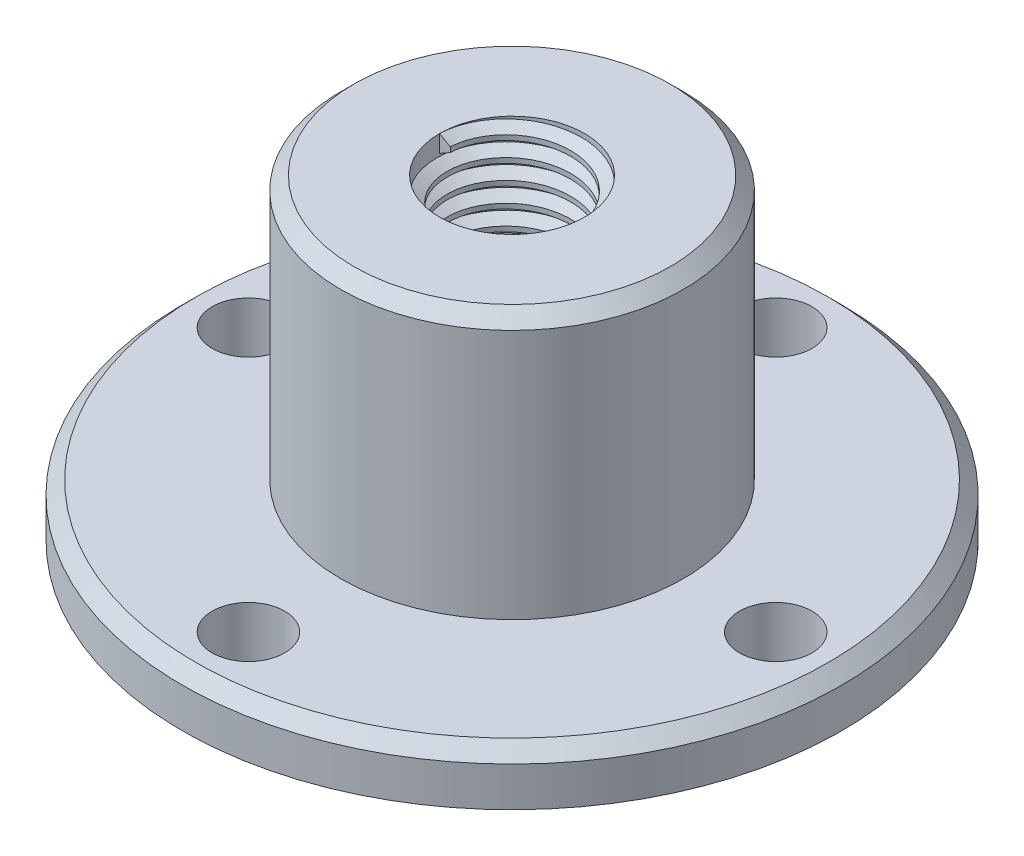
SolidWorks part; units mm, degrees
material "6061 Legierung"
ref_plane "Ebene vorne" through (0, 0, 0) normal (0, 0, 1) x (1, 0, 0)
ref_plane "Ebene oben" through (0, 0, 0) normal (0, 1, 0) x (1, 0, 0)
ref_plane "Ebene rechts" through (0, 0, 0) normal (1, 0, 0) x (0, 0, -1)
sketch "Skizze1" plane through (0, 0, 0) normal (0, 1, 0) x (1, 0, 0)
  circle A0 centre (0, 0) radius 13
  circle A1 centre (0, 0) radius 5.5
  dimension "D1" = 26
  dimension "D2" = 11
extrude "Aufsatz-Linear austragen1" add sketch "Skizze1" along normal blind 20
sketch "Skizze5" plane through (0, 0, 0) normal (0, -1, 0) x (1, 0, 0)
  circle A0 centre (0, 0) radius 25
  circle A2 centre (0, 0) radius 5.5
  dimension "D1" = 50
extrude "Aufsatz-Linear austragen2" add sketch "Skizze5" along normal blind 4
thread "Gewinde1" pitch 1.5 method extrude profile "Gewindeprofil1" start angle 0, offset 0, length 0, pitch 1.5, diameter 11
ref_plane "Ebene1" through (-5.5, 20, 0) normal (0, 0, 1) x (-1, 0, 0)
sketch "Gewindeprofil1" plane through (-5.5, 20, 0) normal (0, 0, 1) x (-1, 0, 0)
  line L0 (0, 0) -> (0, 1.5) construction
  line L11 (0, 0) -> (0, 1.3125)
  line L12 (0, 1.3125) -> (-0.8119, 0.8437)
  line L13 (-0.8119, 0.8437) -> (-0.8119, 0.4687)
  line L15 (-0.8119, 0.4687) -> (0, 0)
  line L17 (-0.8119, 0.6562) -> (0, 0.6562) construction
  point P2 (0, 0)
  dimension "Pitch" = 1.5
  dimension "Profile_Angle" = 60
  dimension "Profile_Land" = 0.375
  dimension "Profile_Height" = 0.8119
hole_wizard "Durchgangsloch für M51" positions "Skizze8" profile "Skizze7" hole size "M5" standard "ISO"
sketch "Skizze8" plane through (0, -4, 0) normal (0, -1, 0) x (-1, 0, 0)
  circle A0 centre (0, 0) radius 20 construction
  point P0 (0, 20)
  point P2 (20, 0)
  point P4 (0, -20)
  point P6 (-20, 0)
  dimension "D1" = 40
sketch "Skizze7" plane through (0, -4, -20) normal (1, 0, 0) x (0, 0, -1)
  line L0 (0, 0) -> (0, 26.6524)
  line L1 (0, 26.6524) -> (2.75, 25)
  line L2 (2.75, 25) -> (2.75, 0)
  line L5 (2.75, 0) -> (0, 0)
  line L10 (0, 26.6524) -> (-2.75, 25) construction
  line L11 (0, -6.35) -> (0, 107.95) construction
  dimension "Bohrerdurchmesser" = 5.5
  dimension "Bohrungstiefe" = 25
  dimension "Spitzenwinkel" = 118
chamfer "Fase1" distance 1 angle 45 2 edges at (0, 20, 13) (0, 0, -25)
sketch "Skizze9" plane through (0, -4, 0) normal (0, -1, 0) x (1, 0, 0)
  circle A0 centre (0, 0) radius 8.0386
extrude "Schnitt-Linear austragen1" cut sketch "Skizze9" along normal blind 10
